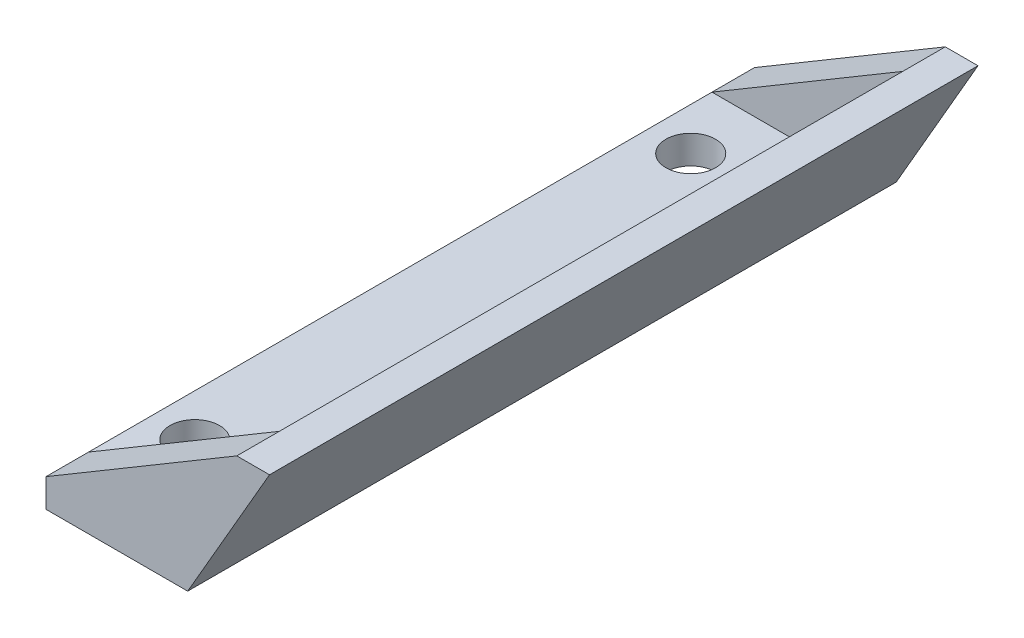
SolidWorks part; units mm, degrees
ref_plane "Front Plane" through (0, 0, 0) normal (0, 0, 1) x (1, 0, 0)
ref_plane "Top Plane" through (0, 0, 0) normal (0, 1, 0) x (1, 0, 0)
ref_plane "Right Plane" through (0, 0, 0) normal (1, 0, 0) x (0, 0, -1)
sketch "Sketch1" plane through (0, 0, 0) normal (0, 0, 1) x (1, 0, 0)
  line L0 (-10, 0) -> (0, 0)
  line L1 (0, 0) -> (5.7735, 10)
  line L2 (5.7735, 10) -> (3.4641, 10)
  line L3 (3.4641, 10) -> (-1.1547, 2)
  line L4 (-1.1547, 2) -> (-10, 2)
  line L5 (-10, 2) -> (-10, 0)
  dimension "D1" = 2
  dimension "D2" = 2
  dimension "D3" = 10
  dimension "D4" = 10
  dimension "D5" = 60
extrude "Boss-Extrude1" add sketch "Sketch1" along normal blind 25 and the other way blind 25
sketch "Sketch2" plane through (0, 0, 0) normal (0, -1, 0) x (1, 0, 0)
  line L0 (-7, 17.5) -> (-7, -17.5) construction
  line L1 (-7, 0) -> (0, 0) construction
  line L2 (-10, -25) -> (-10, 25) construction
  circle A0 centre (-7, 17.5) radius 1.75
  circle A1 centre (-7, -17.5) radius 1.75
  dimension "D3" = 3.5
  dimension "D1" = 3
  dimension "D2" = 35
extrude "Cut-Extrude1" cut sketch "Sketch2" against normal through all
sketch "Sketch3" plane through (0, 0, -25) normal (0, 0, -1) x (-1, 0, 0)
  line L0 (-3.4641, 10) -> (10, 2)
  line L1 (10, 2) -> (1.1547, 2)
  line L2 (1.1547, 2) -> (-3.4641, 10)
extrude "Boss-Extrude2" add sketch "Sketch3" against normal blind 3
mirror "Mirror1" about plane through (0, 0, 0) normal (0, 0, 1) of "Boss-Extrude2"
